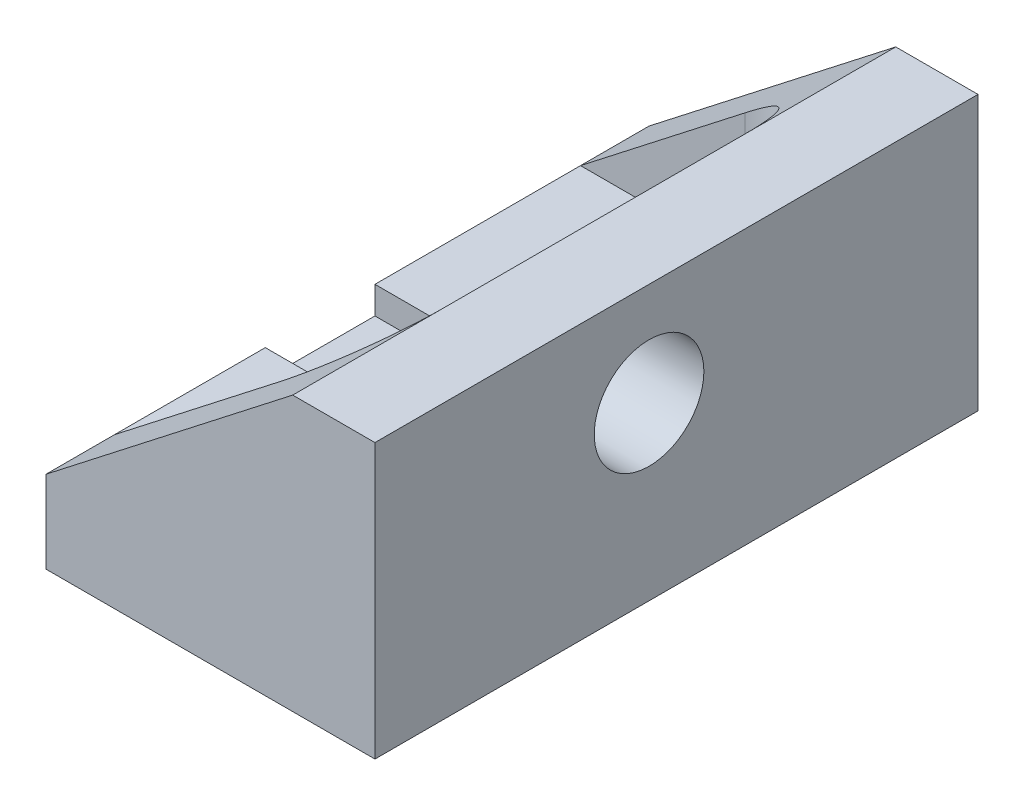
SolidWorks part; units mm, degrees
material "PLA"
ref_plane "前视基准面" through (0, 0, 0) normal (0, 0, 1) x (1, 0, 0)
ref_plane "上视基准面" through (0, 0, 0) normal (0, 1, 0) x (1, 0, 0)
ref_plane "右视基准面" through (0, 0, 0) normal (1, 0, 0) x (0, 0, -1)
sketch "草图1" plane through (0, 0, 0) normal (0, 1, 0) x (1, 0, 0)
  line L1 (-4, -11) -> (4, -11)
  line L2 (-4, -11) -> (-4, 11)
  line L3 (-4, 11) -> (4, 11)
  line L4 (4, -11) -> (4, 11) construction
  line L5 (0, 11) -> (0, -11) construction
  line L6 (-4, 0) -> (4, 0) construction
  line L7 (4, 11) -> (8, 11)
  line L8 (4, 11) -> (4, -11) construction
  line L9 (4, -11) -> (8, -11)
  line L10 (8, 11) -> (8, -11)
  circle A0 centre (0, 6) radius 1.35
  circle A1 centre (0, -6) radius 1.35
  point P0 (0, 0)
  dimension "D1" = 2.7
  dimension "D2" = 12
  dimension "D3" = 22
  dimension "D4" = 8
  dimension "D5" = 12
  dimension "D6" = 5
extrude "凸台-拉伸1" add sketch "草图1" along normal blind 3
sketch "草图2" plane through (0, 3, 0) normal (0, 1, 0) x (1, 0, 0)
  line L1 (5, 11) -> (5, -11)
  line L6 (8, -11) -> (8, 11)
  line L7 (8, 11) -> (-4, 11) construction
  line L12 (0, 0) -> (8, 0) construction
  line L13 (5, 11) -> (8, 11)
  line L14 (5, -11) -> (8, -11)
  line L16 (8, -11) -> (8, 11) construction
  point P0 (0, 0)
  dimension "D2" = 3
extrude "凸台-拉伸2" add sketch "草图2" along normal blind 7
sketch "草图3" plane through (8, 0, 0) normal (1, 0, 0) x (0, 0, -1)
  line L0 (-1, 0) -> (-1, 10) construction
  line L2 (-11, 10) -> (-11, 3) construction
  line L3 (-11, 0) -> (11, 0) construction
  circle A0 centre (-1, 6.25) radius 2
  dimension "D1" = 4
  dimension "D2" = 6.25
  dimension "D3" = 10
extrude "切除-拉伸2" cut sketch "草图3" against normal through all
sketch "草图4" plane through (0, 0, -11) normal (0, 0, -1) x (-1, 0, 0)
  line L0 (-5, 10) -> (-5, 3)
  line L1 (-5, 3) -> (4, 3)
  line L2 (4, 3) -> (-5, 10)
extrude "凸台-拉伸3" add sketch "草图4" against normal blind 2.5
mirror "镜向1" about plane through (0, 0, 0) normal (0, 0, 1) of "凸台-拉伸3"
ref_axis "基准轴1" through (4.2116, 6.25, 1) along (1, 0, 0)
sketch "草图5" plane through (0, 3, 0) normal (0, 1, 0) x (1, 0, 0)
  line L5 (4.2116, -1) -> (8.5709, -1) construction
  line L6 (1.5, 2.25) -> (5, 2.25)
  line L8 (1.5, 2.25) -> (1.5, 1)
  line L12 (1.5, -4.25) -> (5, -4.25)
  line L13 (5, 2.25) -> (5, -4.25)
  line L14 (1.5, 2.25) -> (5, -4.25) construction
  line L15 (1.5, -4.25) -> (5, 2.25) construction
  line L16 (5, 8.5) -> (5, -8.5) construction
  line L17 (-4, 8.5) -> (-4, -8.5) construction
  line L18 (-4, 1) -> (1.5, 1)
  line L19 (-4, 1) -> (-4, -3)
  line L20 (-4, -3) -> (1.5, -3)
  line L22 (-4, 1) -> (1.5, -3) construction
  line L23 (-4, -3) -> (1.5, 1) construction
  line L24 (1.5, -3) -> (1.5, -4.25)
  point P0 (3.25, -1)
  point P9 (-1.25, -1)
  dimension "D3" = 4
  dimension "D1" = 3.5
  dimension "D2" = 6.5
sketch "草图6" [suppressed] plane through (0, 3, 0) normal (0, 1, 0) x (1, 0, 0)
  circle A0 centre (0, -6) radius 2.5 construction
  dimension "D1" = 5
fillet "圆角1" radius 3 2 edges at (5, 6.5, 8.5) (5, 6.5, -8.5)
extrude "切除-拉伸3" cut sketch "草图5" against normal blind 1
